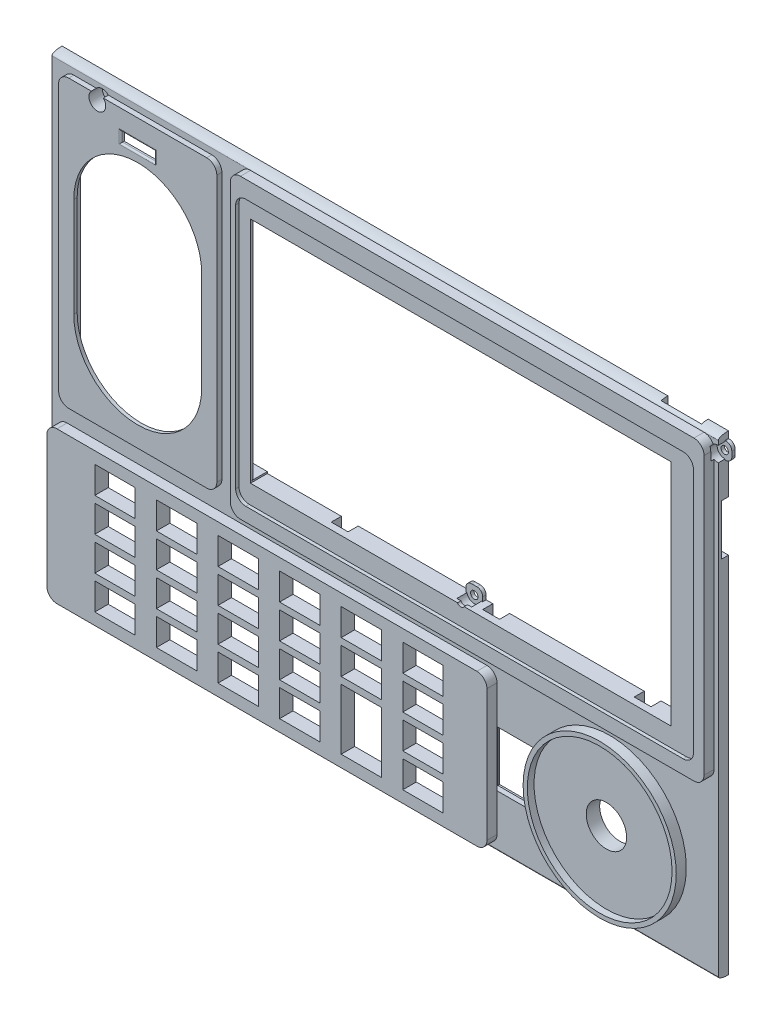
SolidWorks part; units mm, degrees
ref_plane "Front Plane" through (0, 0, 0) normal (0, 0, 1) x (1, 0, 0)
ref_plane "Top Plane" through (0, 0, 0) normal (0, 1, 0) x (1, 0, 0)
ref_plane "Right Plane" through (0, 0, 0) normal (1, 0, 0) x (0, 0, -1)
sketch "Sketch1" plane through (0, 0, 0) normal (0, 0, 1) x (1, 0, 0)
  line L1 (99, -70) -> (-99, -70)
  line L2 (99, -70) -> (99, 70)
  line L3 (99, 70) -> (-99, 70)
  line L4 (-99, -70) -> (-99, 70)
  line L5 (99, -70) -> (-99, 70) construction
  line L6 (99, 70) -> (-99, -70) construction
  point P0 (0, 0)
  dimension "D1" = 198
  dimension "D2" = 140
extrude "main_body" add sketch "Sketch1" along normal blind 3
fillet "long_corners" radius 3 2 edges at (0, 70, 3) (0, -70, 3) second distance 1 first distance on face at (0, 70, 1.5) first distance on face at (0, -70, 1.5)
sketch "Sketch2" plane through (0, 0, 3) normal (0, 0, 1) x (1, 0, 0)
  line L0 (-99, 24.75) -> (99, 24.75) construction
  line L1 (-99, 69) -> (-99, -69) construction
  line L2 (99, -69) -> (99, 69) construction
  line L3 (99, 69) -> (-99, 69) construction
  line L4 (-48.5, -17.75) -> (-95.5, -17.75)
  line L5 (-48.5, -17.75) -> (-48.5, 67.25)
  line L6 (-48.5, 67.25) -> (-95.5, 67.25)
  line L7 (-95.5, -17.75) -> (-95.5, 67.25)
  line L8 (-48.5, -17.75) -> (-95.5, 67.25) construction
  line L9 (-48.5, 67.25) -> (-95.5, -17.75) construction
  point P6 (-72, 24.75)
  dimension "D1" = 85
  dimension "D2" = 47
  dimension "D3" = 27
  dimension "D4" = 44.25
extrude "speaker" add sketch "Sketch2" along normal blind 1.5
fillet "speaker_corners" radius 3 4 edges at (-95.5, 67.25, 3.75) (-95.5, -17.75, 3.75) (-48.5, -17.75, 3.75) (-48.5, 67.25, 3.75)
sketch "Sketch19" plane through (0, 0, 4.5) normal (0, 0, 1) x (1, 0, 0)
  line L0 (-72, 67.25) -> (-72, -17.75) construction
  line L1 (-51.5, 67.25) -> (-92.5, 67.25) construction
  line L2 (-92.5, -17.75) -> (-51.5, -17.75) construction
  line L3 (-72, 7.25) -> (-72, 36.75) construction
  line L4 (-95.5, 64.25) -> (-95.5, -14.75) construction
  line L5 (-95.5, 24.75) -> (-48.5, 24.75) construction
  line L6 (-48.5, -14.75) -> (-48.5, 64.25) construction
  line L7 (-91, 7.25) -> (-91, 36.75)
  line L8 (-53, 7.25) -> (-53, 36.75)
  arc A0 (-91, 7.25) -> (-53, 7.25) centre (-72, 7.25) ccw
  arc A1 (-53, 36.75) -> (-91, 36.75) centre (-72, 36.75) ccw
  point P14 (-72, 22)
  point P19 (-72, -11.75)
  point P20 (-72, 55.75)
  dimension "D2" = 67.5
  dimension "D1" = 38
  dimension "D3" = 11.5
  dimension "D4" = 6
extrude "speaker_cut" cut sketch "Sketch19" against normal through all
sketch "Sketch21" plane through (0, 0, 0) normal (0, 0, -1) x (-1, 0, 0)
  line L0 (72, -11.75) -> (72, 55.75) construction
  line L2 (53, 7.25) -> (53, 36.75) construction
  line L3 (53, 22) -> (91, 22) construction
  line L4 (91, 36.75) -> (91, 7.25) construction
  line L5 (50.5, 61) -> (93.5, 61)
  line L6 (50.5, 61) -> (50.5, -17)
  line L7 (50.5, -17) -> (93.5, -17)
  line L8 (93.5, 61) -> (93.5, -17)
  line L9 (50.5, 61) -> (93.5, -17) construction
  line L10 (50.5, -17) -> (93.5, 61) construction
  arc A0 (53, 7.25) -> (91, 7.25) centre (72, 7.25) ccw construction
  arc A1 (91, 36.75) -> (53, 36.75) centre (72, 36.75) ccw construction
  point P14 (72, 22)
  dimension "D1" = 43
  dimension "D2" = 78
extrude "speaker_slot" cut sketch "Sketch21" against normal blind 3.5
sketch "Sketch3" plane through (0, 0, 3) normal (0, 0, 1) x (1, 0, 0)
  line L0 (-99, 24.875) -> (99, 24.875) construction
  line L1 (-99, 69) -> (-99, -69) construction
  line L2 (99, -69) -> (99, 69) construction
  line L4 (-48.5, -14.75) -> (-48.5, 64.25) construction
  line L5 (97.75, -19.25) -> (-43, -19.25)
  line L6 (97.75, -19.25) -> (97.75, 69)
  line L7 (97.75, 69) -> (-43, 69)
  line L8 (-43, -19.25) -> (-43, 69)
  line L9 (97.75, -19.25) -> (-43, 69) construction
  line L10 (97.75, 69) -> (-43, -19.25) construction
  line L11 (99, 70) -> (-99, 70) construction
  point P8 (27.375, 24.875)
  dimension "D1" = 1
  dimension "D2" = 88.25
  dimension "D3" = 140.75
  dimension "D4" = 1.25
  dimension "D5" = 5.5
extrude "lcd" add sketch "Sketch3" along normal blind 3
fillet "lcd_corners" radius 3 4 edges at (97.75, -19.25, 4.5) (-43, -19.25, 4.5)
sketch "Sketch9" plane through (0, 0, 6) normal (0, 0, 1) x (1, 0, 0)
  line L0 (-43, 24.375) -> (97.75, 24.375) construction
  line L1 (-43, 66) -> (-43, -16.25) construction
  line L2 (97.75, -16.25) -> (97.75, 66) construction
  line L3 (-40, -19.25) -> (94.75, -19.25) construction
  line L4 (94.6, -15.125) -> (-41.4, -15.125)
  line L5 (94.6, -15.125) -> (94.6, 63.875)
  line L6 (94.6, 63.875) -> (-41.4, 63.875)
  line L7 (-41.4, -15.125) -> (-41.4, 63.875)
  line L8 (94.6, -15.125) -> (-41.4, 63.875) construction
  line L9 (94.6, 63.875) -> (-41.4, -15.125) construction
  line L10 (94.75, 69) -> (-40, 69) construction
  line L11 (97.75, -16.25) -> (97.75, 66) construction
  point P6 (26.6, 24.375)
  dimension "D1" = 136
  dimension "D2" = 79
  dimension "D3" = 1.6
  dimension "D4" = 4.125
  dimension "D5" = 5.125
  dimension "D6" = 3.15
extrude "lcd_front" cut sketch "Sketch9" against normal blind 1
fillet "lcd_front_corners" radius 3 4 edges at (94.6, -15.125, 5.5) (94.6, 63.875, 5.5) (-41.4, 63.875, 5.5) (-41.4, -15.125, 5.5)
sketch "Sketch10" plane through (0, 0, 0) normal (0, 0, -1) x (-1, 0, 0)
  line L0 (-94.6, -12.125) -> (-94.6, 60.875) construction
  line L1 (-91.6, 63.875) -> (38.4, 63.875) construction
  line L2 (41.4, 63.875) -> (41.4, -15.125) construction
  line L3 (-94.6, 63.875) -> (41.4, 63.875) construction
  line L4 (38, -9.5) -> (-87, -9.5)
  line L5 (38, -9.5) -> (38, 58.5)
  line L6 (38, 58.5) -> (-87, 58.5)
  line L7 (-87, -9.5) -> (-87, 58.5)
  line L8 (-87, -9.5) -> (38, 58.5) construction
  line L9 (-87, 58.5) -> (38, -9.5) construction
  line L10 (-99, -70) -> (-99, 70) construction
  line L11 (-99, 70) -> (99, 70) construction
  line L13 (38.4, -15.125) -> (-91.6, -15.125) construction
  dimension "D1" = 125
  dimension "D2" = 68
  dimension "D3" = 12
  dimension "D4" = 3.4
  dimension "D5" = 11.5
  dimension "D6" = 5.375
  dimension "D7" = 7.6
  dimension "D8" = 5.375
  dimension "D9" = 5.625
extrude "lcd_back" cut sketch "Sketch10" against normal through all
sketch "Sketch56" plane through (0, 0, 0) normal (0, 0, -1) x (-1, 0, 0)
  line L0 (-87, -9.5) -> (38, -9.5) construction
  line L1 (-79, -9.5) -> (-74, -9.5)
  line L2 (-79, -9.5) -> (-79, -12.5)
  line L3 (-79, -12.5) -> (-74, -12.5)
  line L4 (-74, -9.5) -> (-74, -12.5)
  line L5 (38, 58.5) -> (-87, 58.5) construction
  line L6 (-34, -9.5) -> (-29, -9.5)
  line L7 (-34, -9.5) -> (-34, -12.5)
  line L8 (-34, -12.5) -> (-29, -12.5)
  line L9 (-29, -9.5) -> (-29, -12.5)
  line L10 (11, -9.5) -> (16, -9.5)
  line L11 (11, -9.5) -> (11, -12.5)
  line L12 (11, -12.5) -> (16, -12.5)
  line L13 (16, -9.5) -> (16, -12.5)
  line L14 (-79, 58.5) -> (-74, 58.5)
  line L15 (-79, 58.5) -> (-79, 61.5)
  line L16 (-79, 61.5) -> (-74, 61.5)
  line L17 (-74, 58.5) -> (-74, 61.5)
  line L18 (38, -9.5) -> (38, 58.5) construction
  line L19 (-34, 58.5) -> (-29, 58.5)
  line L20 (-34, 58.5) -> (-34, 61.5)
  line L21 (-34, 61.5) -> (-29, 61.5)
  line L22 (-29, 58.5) -> (-29, 61.5)
  line L23 (11, 58.5) -> (16, 58.5)
  line L24 (11, 58.5) -> (11, 61.5)
  line L25 (11, 61.5) -> (16, 61.5)
  line L26 (16, 58.5) -> (16, 61.5)
  line L27 (38, 58) -> (42, 58)
  line L28 (38, 58) -> (38, -9)
  line L29 (38, -9) -> (42, -9)
  line L30 (42, 58) -> (42, -9)
  line L31 (-99, -70) -> (-99, 70) construction
  line L32 (-99, 70) -> (99, 70) construction
  point P34 (-29, -11)
  dimension "D1" = 5
  dimension "D2" = 5
  dimension "D3" = 5
  dimension "D4" = 5
  dimension "D5" = 5
  dimension "D6" = 5
  dimension "D7" = 67
  dimension "D8" = 4
  dimension "D9" = 3
  dimension "D10" = 3
  dimension "D11" = 3
  dimension "D12" = 3
  dimension "D13" = 3
  dimension "D14" = 3
  dimension "D15" = 40
  dimension "D16" = 40
  dimension "D17" = 20
  dimension "D18" = 20
  dimension "D19" = 40
  dimension "D20" = 40
  dimension "D21" = 12
extrude "lcd_glue_points" cut sketch "Sketch56" against normal blind 3
sketch "Sketch4" plane through (0, 0, 3) normal (0, 0, 1) x (1, 0, 0)
  line L0 (-99, -45.75) -> (99, -45.75) construction
  line L1 (-99, 69) -> (-99, -69) construction
  line L2 (99, -69) -> (99, 69) construction
  line L4 (-92.5, -17.75) -> (-51.5, -17.75) construction
  line L5 (33.25, -68.25) -> (-97.5, -68.25)
  line L6 (33.25, -68.25) -> (33.25, -23.25)
  line L7 (33.25, -23.25) -> (-97.5, -23.25)
  line L8 (-97.5, -68.25) -> (-97.5, -23.25)
  line L9 (33.25, -68.25) -> (-97.5, -23.25) construction
  line L10 (33.25, -23.25) -> (-97.5, -68.25) construction
  line L11 (-99, -70) -> (99, -70) construction
  point P8 (-32.125, -45.75)
  dimension "D1" = 1.75
  dimension "D2" = 130.75
  dimension "D3" = 45
  dimension "D4" = 1.5
  dimension "D5" = 5.5
extrude "keypad" add sketch "Sketch4" along normal blind 3
fillet "keypad_corners" radius 3 4 edges at (-97.5, -68.25, 4.5) (33.25, -68.25, 4.5) (33.25, -23.25, 4.5) (-97.5, -23.25, 4.5)
sketch "Sketch25" plane through (0, 0, 6) normal (0, 0, 1) x (1, 0, 0)
  line L0 (-97.5, -30.75) -> (33.25, -30.75) construction
  line L1 (30.25, -23.25) -> (-94.5, -23.25) construction
  line L2 (-94.5, -68.25) -> (30.25, -68.25) construction
  line L3 (-77.25, -23.25) -> (-77.25, -68.25) construction
  line L5 (-34.65, -64.75) -> (33.25, -64.75) construction
  line L6 (-97.5, -26.25) -> (-97.5, -65.25) construction
  line L11 (33.25, -65.25) -> (33.25, -26.25) construction
  line L12 (-58.95, -23.25) -> (-58.95, -68.25) construction
  line L13 (-97.5, -40.75) -> (33.25, -40.75) construction
  line L14 (30.25, -23.25) -> (-94.5, -23.25) construction
  line L15 (-40.65, -23.25) -> (-40.65, -68.25) construction
  line L16 (-94.5, -68.25) -> (30.25, -68.25) construction
  line L17 (-71.25, -34.75) -> (-83.25, -34.75)
  line L18 (-22.35, -23.25) -> (-22.35, -68.25) construction
  line L19 (-97.5, -50.75) -> (33.25, -50.75) construction
  line L20 (-4.05, -23.25) -> (-4.05, -68.25) construction
  line L21 (-71.25, -34.75) -> (-71.25, -26.75)
  line L22 (14.25, -23.25) -> (14.25, -68.25) construction
  line L23 (-97.5, -26.25) -> (-97.5, -65.25) construction
  line L24 (-97.5, -60.75) -> (33.25, -60.75) construction
  line L25 (-71.25, -26.75) -> (-83.25, -26.75)
  line L26 (-83.25, -34.75) -> (-83.25, -26.75)
  line L27 (-71.25, -34.75) -> (-83.25, -26.75) construction
  line L28 (-71.25, -26.75) -> (-83.25, -34.75) construction
  line L29 (-71.25, -44.75) -> (-83.25, -44.75)
  line L30 (-71.25, -44.75) -> (-71.25, -36.75)
  line L31 (-71.25, -36.75) -> (-83.25, -36.75)
  line L32 (-83.25, -44.75) -> (-83.25, -36.75)
  line L33 (-71.25, -44.75) -> (-83.25, -36.75) construction
  line L34 (-71.25, -36.75) -> (-83.25, -44.75) construction
  line L35 (-71.25, -54.75) -> (-83.25, -54.75)
  line L36 (-71.25, -54.75) -> (-71.25, -46.75)
  line L37 (-71.25, -46.75) -> (-83.25, -46.75)
  line L38 (-83.25, -54.75) -> (-83.25, -46.75)
  line L39 (-71.25, -54.75) -> (-83.25, -46.75) construction
  line L40 (-71.25, -46.75) -> (-83.25, -54.75) construction
  line L41 (-71.25, -64.75) -> (-83.25, -64.75)
  line L42 (-71.25, -64.75) -> (-71.25, -56.75)
  line L43 (-71.25, -56.75) -> (-83.25, -56.75)
  line L44 (-83.25, -64.75) -> (-83.25, -56.75)
  line L45 (-71.25, -64.75) -> (-83.25, -56.75) construction
  line L46 (-71.25, -56.75) -> (-83.25, -64.75) construction
  line L47 (-52.95, -34.75) -> (-64.95, -34.75)
  line L48 (-52.95, -34.75) -> (-52.95, -26.75)
  line L49 (-52.95, -26.75) -> (-64.95, -26.75)
  line L50 (-64.95, -34.75) -> (-64.95, -26.75)
  line L51 (-52.95, -34.75) -> (-64.95, -26.75) construction
  line L52 (-52.95, -26.75) -> (-64.95, -34.75) construction
  line L53 (-52.95, -44.75) -> (-64.95, -44.75)
  line L54 (-52.95, -44.75) -> (-52.95, -36.75)
  line L55 (-52.95, -36.75) -> (-64.95, -36.75)
  line L56 (-64.95, -44.75) -> (-64.95, -36.75)
  line L57 (-52.95, -44.75) -> (-64.95, -36.75) construction
  line L58 (-52.95, -36.75) -> (-64.95, -44.75) construction
  line L59 (-52.95, -54.75) -> (-64.95, -54.75)
  line L60 (-52.95, -54.75) -> (-52.95, -46.75)
  line L61 (-52.95, -46.75) -> (-64.95, -46.75)
  line L62 (-64.95, -54.75) -> (-64.95, -46.75)
  line L63 (-52.95, -54.75) -> (-64.95, -46.75) construction
  line L64 (-52.95, -46.75) -> (-64.95, -54.75) construction
  line L65 (-52.95, -64.75) -> (-64.95, -64.75)
  line L66 (-52.95, -64.75) -> (-52.95, -56.75)
  line L67 (-52.95, -56.75) -> (-64.95, -56.75)
  line L68 (-64.95, -64.75) -> (-64.95, -56.75)
  line L69 (-52.95, -64.75) -> (-64.95, -56.75) construction
  line L70 (-52.95, -56.75) -> (-64.95, -64.75) construction
  line L71 (-34.65, -34.75) -> (-46.65, -34.75)
  line L72 (-34.65, -34.75) -> (-34.65, -26.75)
  line L73 (-34.65, -26.75) -> (-46.65, -26.75)
  line L74 (-46.65, -34.75) -> (-46.65, -26.75)
  line L75 (-34.65, -34.75) -> (-46.65, -26.75) construction
  line L76 (-34.65, -26.75) -> (-46.65, -34.75) construction
  line L77 (-34.65, -44.75) -> (-46.65, -44.75)
  line L78 (-34.65, -44.75) -> (-34.65, -36.75)
  line L79 (-34.65, -36.75) -> (-46.65, -36.75)
  line L80 (-46.65, -44.75) -> (-46.65, -36.75)
  line L81 (-34.65, -44.75) -> (-46.65, -36.75) construction
  line L82 (-34.65, -36.75) -> (-46.65, -44.75) construction
  line L83 (-34.65, -54.75) -> (-46.65, -54.75)
  line L84 (-34.65, -54.75) -> (-34.65, -46.75)
  line L85 (-34.65, -46.75) -> (-46.65, -46.75)
  line L86 (-46.65, -54.75) -> (-46.65, -46.75)
  line L87 (-34.65, -54.75) -> (-46.65, -46.75) construction
  line L88 (-34.65, -46.75) -> (-46.65, -54.75) construction
  line L89 (-34.65, -64.75) -> (-46.65, -64.75)
  line L90 (-34.65, -64.75) -> (-34.65, -56.75)
  line L91 (-34.65, -56.75) -> (-46.65, -56.75)
  line L92 (-46.65, -64.75) -> (-46.65, -56.75)
  line L93 (-34.65, -64.75) -> (-46.65, -56.75) construction
  line L94 (-34.65, -56.75) -> (-46.65, -64.75) construction
  line L95 (-16.35, -34.75) -> (-28.35, -34.75)
  line L96 (-16.35, -34.75) -> (-16.35, -26.75)
  line L97 (-16.35, -26.75) -> (-28.35, -26.75)
  line L98 (-28.35, -34.75) -> (-28.35, -26.75)
  line L99 (-16.35, -34.75) -> (-28.35, -26.75) construction
  line L100 (-16.35, -26.75) -> (-28.35, -34.75) construction
  line L101 (-16.35, -44.75) -> (-28.35, -44.75)
  line L102 (-16.35, -44.75) -> (-16.35, -36.75)
  line L103 (-16.35, -36.75) -> (-28.35, -36.75)
  line L104 (-28.35, -44.75) -> (-28.35, -36.75)
  line L105 (-16.35, -44.75) -> (-28.35, -36.75) construction
  line L106 (-16.35, -36.75) -> (-28.35, -44.75) construction
  line L111 (-16.35, -54.75) -> (-28.35, -54.75)
  line L112 (-16.35, -54.75) -> (-16.35, -46.75)
  line L113 (-16.35, -46.75) -> (-28.35, -46.75)
  line L114 (-28.35, -54.75) -> (-28.35, -46.75)
  line L115 (-16.35, -54.75) -> (-28.35, -46.75) construction
  line L116 (-16.35, -46.75) -> (-28.35, -54.75) construction
  line L117 (-16.35, -64.75) -> (-28.35, -64.75)
  line L118 (-16.35, -64.75) -> (-16.35, -56.75)
  line L119 (-16.35, -56.75) -> (-28.35, -56.75)
  line L120 (-28.35, -64.75) -> (-28.35, -56.75)
  line L121 (-16.35, -64.75) -> (-28.35, -56.75) construction
  line L122 (-16.35, -56.75) -> (-28.35, -64.75) construction
  line L127 (1.95, -34.75) -> (-10.05, -34.75)
  line L128 (1.95, -34.75) -> (1.95, -26.75)
  line L129 (1.95, -26.75) -> (-10.05, -26.75)
  line L130 (-10.05, -34.75) -> (-10.05, -26.75)
  line L131 (1.95, -34.75) -> (-10.05, -26.75) construction
  line L132 (1.95, -26.75) -> (-10.05, -34.75) construction
  line L133 (20.25, -34.75) -> (8.25, -34.75)
  line L134 (20.25, -34.75) -> (20.25, -26.75)
  line L135 (20.25, -26.75) -> (8.25, -26.75)
  line L136 (8.25, -34.75) -> (8.25, -26.75)
  line L137 (20.25, -34.75) -> (8.25, -26.75) construction
  line L138 (20.25, -26.75) -> (8.25, -34.75) construction
  line L139 (1.95, -44.75) -> (-10.05, -44.75)
  line L140 (1.95, -44.75) -> (1.95, -36.75)
  line L141 (1.95, -36.75) -> (-10.05, -36.75)
  line L142 (-10.05, -44.75) -> (-10.05, -36.75)
  line L143 (1.95, -44.75) -> (-10.05, -36.75) construction
  line L144 (1.95, -36.75) -> (-10.05, -44.75) construction
  line L145 (20.25, -44.75) -> (8.25, -44.75)
  line L146 (20.25, -44.75) -> (20.25, -36.75)
  line L147 (20.25, -36.75) -> (8.25, -36.75)
  line L148 (8.25, -44.75) -> (8.25, -36.75)
  line L149 (20.25, -44.75) -> (8.25, -36.75) construction
  line L150 (20.25, -36.75) -> (8.25, -44.75) construction
  line L151 (20.25, -54.75) -> (8.25, -54.75)
  line L152 (20.25, -54.75) -> (20.25, -46.75)
  line L153 (20.25, -46.75) -> (8.25, -46.75)
  line L154 (8.25, -54.75) -> (8.25, -46.75)
  line L155 (20.25, -54.75) -> (8.25, -46.75) construction
  line L156 (20.25, -46.75) -> (8.25, -54.75) construction
  line L157 (20.25, -64.75) -> (8.25, -64.75)
  line L158 (20.25, -64.75) -> (20.25, -56.75)
  line L159 (20.25, -56.75) -> (8.25, -56.75)
  line L160 (8.25, -64.75) -> (8.25, -56.75)
  line L161 (20.25, -64.75) -> (8.25, -56.75) construction
  line L162 (20.25, -56.75) -> (8.25, -64.75) construction
  line L163 (1.95, -64.75) -> (-10.05, -64.75)
  line L164 (1.95, -64.75) -> (1.95, -46.75)
  line L165 (1.95, -46.75) -> (-10.05, -46.75)
  line L166 (-10.05, -64.75) -> (-10.05, -46.75)
  line L167 (1.95, -64.75) -> (-10.05, -46.75) construction
  line L168 (1.95, -46.75) -> (-10.05, -64.75) construction
  point P34 (-77.25, -30.75)
  point P39 (-77.25, -40.75)
  point P44 (-77.25, -50.75)
  point P49 (-77.25, -60.75)
  point P54 (-58.95, -30.75)
  point P59 (-58.95, -40.75)
  point P64 (-58.95, -50.75)
  point P69 (-58.95, -60.75)
  point P74 (-40.65, -30.75)
  point P79 (-40.65, -40.75)
  point P84 (-40.65, -50.75)
  point P89 (-40.65, -60.75)
  point P94 (-22.35, -30.75)
  point P99 (-22.35, -40.75)
  point P104 (-22.35, -50.75)
  point P109 (-22.35, -60.75)
  point P114 (-4.05, -30.75)
  point P119 (14.25, -30.75)
  point P124 (-4.05, -40.75)
  point P129 (14.25, -40.75)
  point P134 (14.25, -50.75)
  point P139 (14.25, -60.75)
  point P144 (-4.05, -55.75)
  dimension "D1" = 19
  dimension "D2" = 18.3
  dimension "D3" = 18.3
  dimension "D4" = 18.3
  dimension "D5" = 18.3
  dimension "D6" = 18.3
  dimension "D7" = 20.25
  dimension "D8" = 7.5
  dimension "D9" = 10
  dimension "D10" = 10
  dimension "D11" = 10
  dimension "D12" = 7.5
  dimension "D13" = 12
  dimension "D14" = 12
  dimension "D15" = 12
  dimension "D16" = 12
  dimension "D17" = 12
  dimension "D18" = 12
  dimension "D19" = 12
  dimension "D20" = 12
  dimension "D21" = 12
  dimension "D22" = 12
  dimension "D23" = 12
  dimension "D24" = 12
  dimension "D25" = 12
  dimension "D26" = 12
  dimension "D27" = 12
  dimension "D28" = 12
  dimension "D29" = 12
  dimension "D30" = 12
  dimension "D31" = 12
  dimension "D32" = 12
  dimension "D33" = 12
  dimension "D34" = 12
  dimension "D35" = 12
  dimension "D36" = 8
  dimension "D37" = 8
  dimension "D38" = 8
  dimension "D39" = 8
  dimension "D40" = 8
  dimension "D41" = 8
  dimension "D42" = 18
  dimension "D43" = 8
  dimension "D44" = 8
  dimension "D45" = 8
  dimension "D46" = 8
  dimension "D47" = 8
  dimension "D48" = 8
  dimension "D49" = 8
  dimension "D50" = 8
  dimension "D51" = 8
  dimension "D52" = 8
  dimension "D53" = 8
  dimension "D54" = 8
  dimension "D55" = 8
  dimension "D56" = 8
  dimension "D57" = 8
  dimension "D58" = 8
  dimension "D59" = 5
extrude "keypad_cuts_0.8" cut sketch "Sketch25" against normal through all
sketch "Sketch5" plane through (0, 0, 3) normal (0, 0, 1) x (1, 0, 0)
  line L0 (33.25, -45.75) -> (99, -45.75) construction
  line L1 (33.25, -65.25) -> (33.25, -26.25) construction
  line L2 (99, -69) -> (99, 69) construction
  circle A0 centre (66.75, -45.75) radius 22.75
  dimension "D1" = 45.5
  dimension "D2" = 32.25
  dimension "D3" = 33.5
extrude "vfo" add sketch "Sketch5" along normal blind 3
sketch "Sketch7" plane through (0, 0, 6) normal (0, 0, 1) x (1, 0, 0)
  line L0 (44, -45.75) -> (89.5, -45.75) construction
  line L1 (66.75, -23) -> (66.75, -68.5) construction
  circle A0 centre (66.75, -45.75) radius 22.75 construction
  circle A1 centre (66.75, -45.75) radius 22.75 construction
  circle A2 centre (66.75, -45.75) radius 6
  dimension "D1" = 12
extrude "vfo_encoder_knob_cut" cut sketch "Sketch7" against normal through all
sketch "esp32" plane through (0, 0, 0) normal (0, 0, -1) x (-1, 0, 0)
  line L0 (99, -70) -> (-99, -70) construction
  line L1 (-50.5, -37.5) -> (-32, -37.5)
  line L2 (-50.5, -37.5) -> (-50.5, -54)
  line L3 (-50.5, -54) -> (-32, -54)
  line L4 (-32, -37.5) -> (-32, -54)
  line L5 (-99, -70) -> (-99, 70) construction
  dimension "D1" = 16
  dimension "D2" = 48.5
  dimension "D3" = 16.5
  dimension "D4" = 18.5
extrude "esp32_can_cut" cut sketch "esp32" against normal blind 3
sketch "Sketch47" plane through (0, 0, 0) normal (0, 0, -1) x (-1, 0, 0)
  line L0 (-50.5, -54) -> (-32, -54) construction
  line L1 (-31, -55) -> (-58, -55)
  line L2 (-31, -55) -> (-31, -36.5)
  line L3 (-31, -36.5) -> (-58, -36.5)
  line L4 (-58, -55) -> (-58, -36.5)
  line L5 (-31, -55) -> (-58, -36.5) construction
  line L6 (-31, -36.5) -> (-58, -55) construction
  line L7 (-50.5, -37.5) -> (-50.5, -54) construction
  point P0 (-44.5, -45.75)
  dimension "D1" = 27
  dimension "D2" = 18.5
  dimension "D3" = 1
  dimension "D4" = 7.5
extrude "esp32_ex_cut" cut sketch "Sketch47" against normal blind 1.5
sketch "Sketch49" plane through (0, 0, 0) normal (0, 0, -1) x (-1, 0, 0)
  line L0 (72, 59.75) -> (72, 67.25) construction
  line L3 (51.5, 67.25) -> (92.5, 67.25) construction
  line L4 (77, 58.25) -> (67, 58.25)
  line L5 (77, 58.25) -> (77, 61.25)
  line L6 (77, 61.25) -> (67, 61.25)
  line L7 (67, 58.25) -> (67, 61.25)
  line L8 (77, 58.25) -> (67, 61.25) construction
  line L9 (77, 61.25) -> (67, 58.25) construction
  point P6 (72, 59.75)
  dimension "D1" = 10
  dimension "D2" = 3
  dimension "D3" = 7.5
extrude "amb_sensor" cut sketch "Sketch49" against normal through all
fillet "amb_corners" radius 0.5 4 edges at (-67, 59.75, 4.5) (-72, 61.25, 4.5) (-77, 59.75, 4.5) (-72, 58.25, 4.5)
sketch "Sketch55" plane through (0, 0, 0) normal (0, 0, -1) x (-1, 0, 0)
  line L0 (-99, -70) -> (-99, 70) construction
  line L5 (-93, 70) -> (-81, 70)
  line L6 (-93, 70) -> (-93, 58.5)
  line L11 (-93, 58.5) -> (-81, 58.5)
  line L12 (-81, 70) -> (-81, 58.5)
  line L13 (94.5, 48) -> (99, 48)
  line L14 (94.5, 48) -> (94.5, 33)
  line L15 (94.5, 33) -> (99, 33)
  line L16 (99, 48) -> (99, 33)
  line L17 (94.5, 48) -> (99, 33) construction
  line L18 (94.5, 33) -> (99, 48) construction
  line L23 (99, 65.5) -> (-99, 65.5) construction
  line L24 (99, -8.5) -> (-99, -8.5) construction
  line L35 (-99, -68) -> (99, -68) construction
  line L36 (99, -70) -> (-99, -70) construction
  line L42 (-99, 53) -> (-93, 53)
  line L43 (-99, 53) -> (-99, 38)
  line L44 (-99, 70) -> (99, 70) construction
  line L45 (-99, 38) -> (-93, 38)
  line L46 (99, 70) -> (99, -70) construction
  line L47 (-93, 53) -> (-93, 38)
  circle A1 centre (49.5, 65.5) radius 3
  circle A2 centre (-24.5, 65.5) radius 3
  circle A4 centre (49.5, -8.5) radius 3
  circle A6 centre (-68, -68) radius 3
  circle A7 centre (-1, -68) radius 3
  circle A9 centre (-32, 65.5) radius 3
  point P10 (96.75, 40.5)
  dimension "D8" = 6
  dimension "D9" = 6
  dimension "D13" = 6
  dimension "D18" = 2
  dimension "D19" = 6
  dimension "D21" = 6
  dimension "D22" = 6
  dimension "D1" = 12
  dimension "D3" = 11.5
  dimension "D4" = 0
  dimension "D5" = 6
  dimension "D6" = 4.5
  dimension "D11" = 49.5
  dimension "D12" = 123.5
  dimension "D14" = 7.5
  dimension "D15" = 61.5
  dimension "D24" = 100
  dimension "D25" = 15
  dimension "D26" = 4.5
  dimension "D27" = 0
  dimension "D28" = 22
  dimension "D29" = 49.5
  dimension "D30" = 67
  dimension "D31" = 6
  dimension "D32" = 15
  dimension "D33" = 0
  dimension "D34" = 17
extrude "conn_cutouts" cut sketch "Sketch55" against normal blind 2
fillet "Fillet1" radius 2 1 edges at (-38, 24.5, 3)
fillet "Fillet2" radius 5 1 edges at (-42, 24.5, 0)
sketch "Sketch57" plane through (0, 0, 0) normal (0, 0, -1) x (-1, 0, 0)
  line L0 (99, 70) -> (99, 48) construction
  line L1 (-24, -22) -> (89, -22)
  line L2 (-24, -22) -> (-24, -67.5)
  line L3 (-24, -67.5) -> (89, -67.5)
  line L4 (89, -22) -> (89, -67.5)
  line L5 (99, -70) -> (1.2361, -70) construction
  dimension "D1" = 113
  dimension "D2" = 45.5
  dimension "D3" = 10
  dimension "D4" = 2.5
extrude "keyboard_back" cut sketch "Sketch57" against normal blind 2
sketch "Sketch58" plane through (0, -9.5, 0) normal (0, 1, 0) x (1, 0, 0)
  line L1 (27, -1) -> (22, -1)
  line L2 (27, -1) -> (27, 0)
  line L3 (27, 0) -> (22, 0)
  line L4 (22, -1) -> (22, 0)
  line L5 (27, -1) -> (22, 0) construction
  line L6 (27, 0) -> (22, -1) construction
  line L7 (29, -3) -> (29, 0) construction
  line L9 (29, 0) -> (-11, 0) construction
  point P0 (24.5, -0.5)
  dimension "D1" = 1
  dimension "D2" = 5
  dimension "D3" = 2
  dimension "D4" = 0
extrude "behind_lcd_screew_mount" add sketch "Sketch58" along normal blind 3
sketch "Sketch59" plane through (-99, 0, 0) normal (-1, 0, 0) x (0, 0, 1)
  line L0 (0, 70) -> (0, 48) construction
  line L1 (0, -66.5) -> (1, -66.5)
  line L2 (0, -66.5) -> (0, -69.5)
  line L3 (0, -69.5) -> (1, -69.5)
  line L4 (1, -66.5) -> (1, -69.5)
  dimension "D1" = 1
  dimension "D2" = 3
  dimension "D3" = 66.5
extrude "keyb_screw_mount" add sketch "Sketch59" along normal blind 1
sketch "Sketch60" plane through (99, 0, 0) normal (1, 0, 0) x (0, 0, -1)
  line L0 (0, -70) -> (0, 38) construction
  line L1 (0, 68) -> (-1, 68)
  line L2 (0, 68) -> (0, 63)
  line L3 (0, 63) -> (-1, 63)
  line L4 (-1, 68) -> (-1, 63)
  dimension "D1" = 63
  dimension "D2" = 5
  dimension "D3" = 1
extrude "right_corner_screw_mount" add sketch "Sketch60" along normal blind 2
sketch "Sketch61" plane through (0, 0, 0) normal (0, 0, -1) x (-1, 0, 0)
  line L0 (-99, 70) -> (-93, 70) construction
  line L1 (-99, 68) -> (-99, 70) construction
  line L2 (-99, -9) -> (99, -9) construction
  line L3 (99, 70) -> (99, 48) construction
  line L5 (-99, -70) -> (-99, 38) construction
  line L6 (99, 70) -> (99, 48) construction
  line L7 (-3.2361, -70) -> (-65.7639, -70) construction
  line L8 (99, -69.5) -> (99, -70) construction
  line L9 (99, -70) -> (1.2361, -70) construction
  line L10 (-81, 70) -> (99, 70) construction
  circle A0 centre (-98.9, 65.5) radius 1.1
  circle A1 centre (-24.5, -9) radius 1.1
  circle A2 centre (98, -68) radius 1.1
  circle A3 centre (84, 65.5) radius 1.1
  dimension "D1" = 2.2
  dimension "D6" = 2.2
  dimension "D9" = 2.2
  dimension "D10" = 2.2
  dimension "D2" = 4.5
  dimension "D3" = 0.1
  dimension "D4" = 61
  dimension "D5" = 123.5
  dimension "D7" = 1
  dimension "D8" = 2
  dimension "D11" = 15
  dimension "D12" = 4.5
extrude "ui_screws" cut sketch "Sketch61" against normal through all
sketch "Sketch62" plane through (0, 0, 6) normal (0, 0, 1) x (1, 0, 0)
  line L0 (97.8, 65.5) -> (100, 65.5) construction
  line L1 (-98, -66.9) -> (-98, -69.1) construction
  line L2 (98.9, 66.6) -> (98.9, 64.4) construction
  line L4 (-96.9, -68) -> (-99.1, -68) construction
  circle A0 centre (24.5, -9) radius 2.25
  arc A1 (99, 66.5954) -> (99, 64.4046) centre (98.9, 65.5) ccw construction
  arc A2 (99, 64.4046) -> (99, 66.5954) centre (98.9, 65.5) ccw construction
  circle A3 centre (98.9, 65.5) radius 2.25
  arc A4 (-97.5417, -69) -> (-99, -67.5417) centre (-98, -68) ccw construction
  arc A5 (-98.4583, -69) -> (-97.5417, -69) centre (-98, -68) ccw construction
  arc A6 (-99, -67.5417) -> (-99, -68.4583) centre (-98, -68) ccw construction
  circle A7 centre (-98, -68) radius 2.25
  dimension "D1" = 4.5
  dimension "D2" = 4.5
  dimension "D3" = 4.5
extrude "ui_screw_head" cut sketch "Sketch62" against normal blind 3 from offset 2 offset against normal yes
fillet "ui_screw_mount_corners" radius 1.75 6 edges at (-100, -66.5, 0.5) (-100, -69.5, 0.5) (101, 63, 0.5) (101, 68, 0.5) (22, -6.5, 0.5) (27, -6.5, 0.5)
sketch "Sketch63" plane through (0, 0, 6) normal (0, 0, 1) x (1, 0, 0)
  circle A0 centre (66.75, -45.75) radius 21.5
  dimension "D1" = 43
extrude "enc_knob_slot" cut sketch "Sketch63" against normal blind 2
sketch "Sketch64" plane through (0, 0, 4.5) normal (0, 0, 1) x (1, 0, 0)
  circle A0 centre (-84, 65.5) radius 2.5
  dimension "D1" = 5
extrude "on_speaker_ui_screw_head" cut sketch "Sketch64" against normal blind 4
